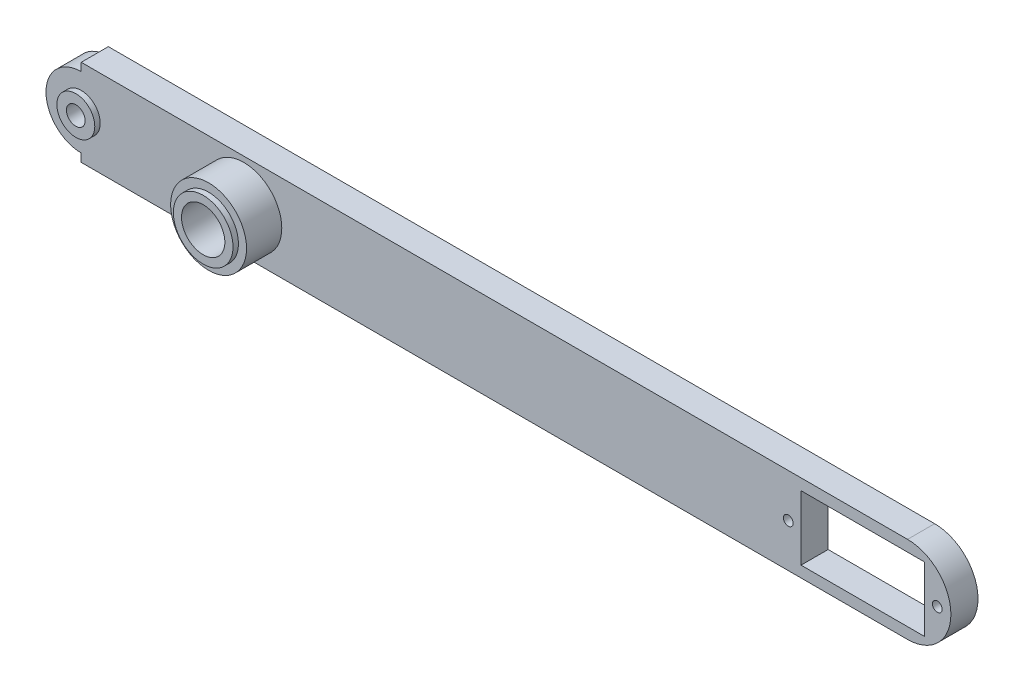
SolidWorks part; units mm, degrees
ref_plane "Front Plane" through (0, 0, 0) normal (0, 0, 1) x (1, 0, 0)
ref_plane "Top Plane" through (0, 0, 0) normal (0, 1, 0) x (1, 0, 0)
ref_plane "Right Plane" through (0, 0, 0) normal (1, 0, 0) x (0, 0, -1)
sketch "Sketch1" plane through (0, 0, 0) normal (0, 0, 1) x (1, 0, 0)
  line L0 (-30, -8) -> (122.45, -8)
  line L1 (122.45, -8) -> (122.45, 8)
  line L2 (122.45, 8) -> (-30, 8)
  line L3 (-30, 8) -> (-30, -8)
extrude "Boss-Extrude1" add sketch "Sketch1" along normal blind 5 from offset 9 offset against normal yes
sketch "Sketch2" plane through (0, 0, 0) normal (0, 0, 1) x (1, 0, 0)
  circle A0 centre (-30, 0) radius 6.5
extrude "Boss-Extrude2" add sketch "Sketch2" along normal blind 5 from offset 9 offset against normal yes
sketch "Sketch3" plane through (0, 0, 0) normal (0, 0, 1) x (1, 0, 0)
  circle A0 centre (122.45, 0) radius 8
extrude "Boss-Extrude3" add sketch "Sketch3" along normal blind 5 from offset 9 offset against normal yes
sketch "Sketch4" plane through (0, 0, 0) normal (0, 0, 1) x (1, 0, 0)
  circle A0 centre (0, 0) radius 7
extrude "Boss-Extrude4" add sketch "Sketch4" along normal blind 11.5 from offset 9 offset against normal yes
sketch "Sketch5" plane through (0, 0, 0) normal (0, 0, 1) x (1, 0, 0)
  circle A0 centre (0, 0) radius 5.5
extrude "Boss-Extrude5" add sketch "Sketch5" along normal blind 1 from offset 2.5
sketch "Sketch6" plane through (0, 0, 0) normal (0, 0, 1) x (1, 0, 0)
  circle A0 centre (-30, 0) radius 3.5
extrude "Boss-Extrude6" add sketch "Sketch6" along normal blind 1 from offset 4 offset against normal yes
sketch "Sketch7" plane through (0, 0, 0) normal (0, 0, 1) x (1, 0, 0)
  circle A0 centre (0, 0) radius 4
extrude "Cut-Extrude1" cut sketch "Sketch7" against normal through all and the other way through all
sketch "Sketch8" plane through (0, 0, 0) normal (0, 0, 1) x (1, 0, 0)
  circle A0 centre (-30, 0) radius 1.725
extrude "Cut-Extrude2" cut sketch "Sketch8" against normal through all and the other way through all
sketch "Sketch9" plane through (0, 0, 0) normal (0, 0, 1) x (1, 0, 0)
  line L0 (102.8, -5.95) -> (125.6, -5.95)
  line L1 (125.6, -5.95) -> (125.6, 5.95)
  line L2 (125.6, 5.95) -> (102.8, 5.95)
  line L3 (102.8, 5.95) -> (102.8, -5.95)
extrude "Cut-Extrude3" cut sketch "Sketch9" against normal through all and the other way through all
sketch "Sketch10" plane through (0, 0, 0) normal (0, 0, 1) x (1, 0, 0)
  circle A0 centre (100.45, 0) radius 0.9
  circle A1 centre (127.95, 0) radius 0.9
extrude "Cut-Extrude4" cut sketch "Sketch10" against normal through all and the other way through all
